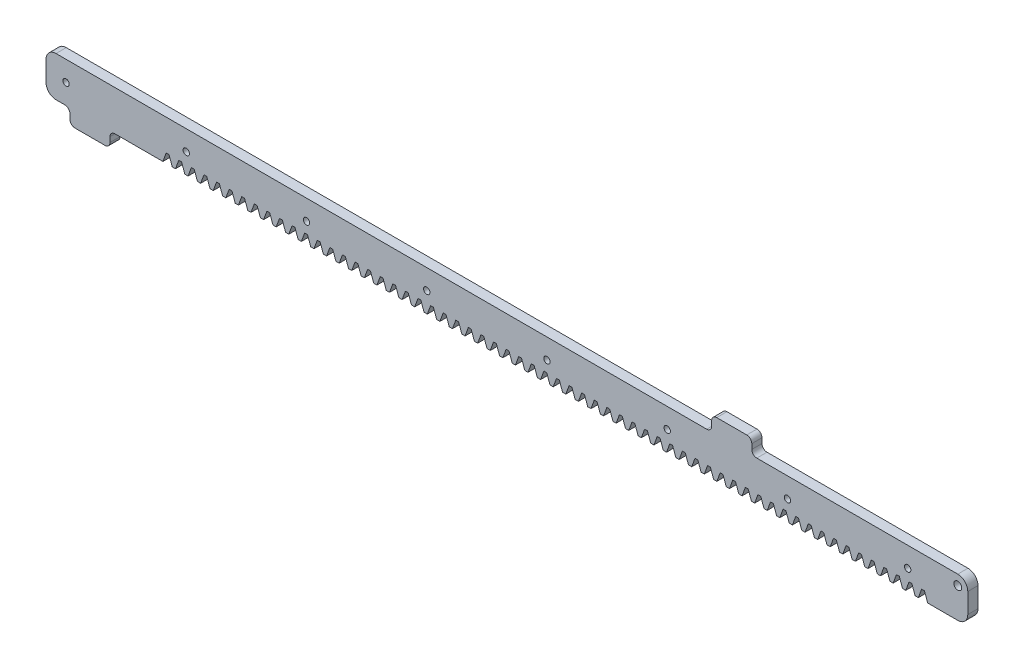
SolidWorks part; units mm, degrees
material "PC High Viscosity"
ref_plane "Front Plane" through (0, 0, 0) normal (0, 0, 1) x (1, 0, 0)
ref_plane "Top Plane" through (0, 0, 0) normal (0, 1, 0) x (1, 0, 0)
ref_plane "Right Plane" through (0, 0, 0) normal (1, 0, 0) x (0, 0, -1)
sketch "Sketch1" plane through (0, 0, 0) normal (0, 0, 1) x (1, 0, 0)
  line L1 (0, 0) -> (15.1307, 0)
  line L2 (0, 0) -> (0, 25.4)
  line L3 (0, 25.4) -> (40.5308, 25.4)
  line L4 (584.2, 0) -> (584.2, 25.4)
  line L7 (533.4, 25.4) -> (584.2, 25.4)
  line L8 (40.5308, 25.4) -> (421.9033, 25.4)
  line L9 (40.5307, 0) -> (584.2, 0)
  line L11 (584.2, 22.7162) -> (577.85, 26.3823) construction
  line L12 (577.85, 26.3823) -> (571.5, 22.7162) construction
  line L13 (571.5, 22.7162) -> (571.5, 15.3838) construction
  line L14 (571.5, 15.3838) -> (577.85, 11.7177) construction
  line L15 (577.85, 11.7177) -> (584.2, 15.3838) construction
  line L16 (584.2, 15.3838) -> (584.2, 22.7162) construction
  line L19 (590.55, 0) -> (590.55, 10.0162) construction
  line L20 (590.55, 10.0162) -> (76.2, 10.0162) construction
  line L21 (76.2, 10.0162) -> (76.2, 0) construction
  line L22 (447.3033, 25.4) -> (533.4, 25.4)
  line L26 (15.1307, 0) -> (15.1307, -9.525)
  line L27 (15.1307, -9.525) -> (40.5307, -9.525)
  line L28 (40.5307, -9.525) -> (40.5307, 0)
  line L29 (421.9033, 25.4) -> (421.9033, 34.925)
  line L30 (421.9033, 34.925) -> (447.3033, 34.925)
  line L31 (447.3033, 34.925) -> (447.3033, 25.4)
  circle A0 centre (577.85, 19.05) radius 2.4892
  circle A1 centre (577.85, 19.05) radius 6.35 construction
  dimension "D5" = 4.9784
  dimension "D6" = 40.5307
  dimension "D7" = 12.7
  dimension "D1" = 584.2
  dimension "D2" = 25.4
  dimension "D3" = 421.9033
  dimension "D4" = 9.525
  dimension "D8" = 25.4
  dimension "D9" = 25.4
extrude "Boss-Extrude1" add sketch "Sketch1" along normal blind 6.477 contours L3 | L1 L4 L3 L2 A0 | L1 region at (289.8115, 12.6919, 0)
fillet "Fillet2" radius 6.35 4 edges at (0, 0, 3.2385) (0, 25.4, 3.2385) (584.2, 25.4, 3.2385) (584.2, 0, 3.2385)
sketch "Sketch2" plane through (0, 0, 6.477) normal (0, 0, 1) x (1, 0, 0)
  line L0 (558.8, 0) -> (43.7057, 0)
  line L1 (43.7057, 0) -> (43.7057, 5.715)
  line L2 (43.7057, 5.715) -> (558.8, 5.715)
  line L3 (558.8, 5.715) -> (558.8, 0)
  line L5 (557.8755, 2.54) -> (549.711, 2.54) construction
  line L6 (558.8, 0) -> (556.7199, 5.715)
  line L7 (40.5307, 0) -> (552.8688, 0) construction
  line L8 (552.8688, 0) -> (558.8, 0)
  line L10 (556.7199, 5.715) -> (554.9488, 5.715)
  line L11 (558.8, 0) -> (552.8688, 0)
  line L12 (552.8688, 0) -> (554.9488, 5.715)
  line L13 (554.9488, 5.715) -> (556.7199, 5.715)
  line L14 (558.8, 0) -> (552.8688, 0)
  line L15 (554.9488, 5.715) -> (556.7199, 5.715)
  line L16 (558.8, 0) -> (552.8688, 0)
  line L17 (552.8688, 0) -> (558.8, 0)
  line L19 (556.7199, 5.715) -> (554.9488, 5.715) construction
  line L20 (552.8688, 0) -> (558.8, 0) construction
  line L21 (0, 0) -> (15.1307, 0) construction
  line L22 (584.2, 0) -> (584.2, 25.4) construction
  line L23 (40.5307, 0) -> (584.2, 0) construction
  point P8 (553.7932, 2.54)
  point P16 (557.8755, 2.54)
  dimension "D1" = 70
  dimension "D2" = 2.54
  dimension "D3" = 3.175
  dimension "D4" = 70
  dimension "D5" = 1.7711
  dimension "D6" = 25.4
extrude "Cut-Extrude1" cut sketch "Sketch2" against normal through all contours L12 L0 L8 L6 L2 region at (555.8344, 2.343, 6.477)
pattern_linear "LPattern1" count 61 spacing 7.9796 along (-1, 0, 0) of "Cut-Extrude1"
sketch "Sketch3" plane through (0, 0, 6.477) normal (0, 0, 1) x (1, 0, 0)
  line L2 (533.4, 25.4) -> (584.2, 25.4) construction
  line L3 (584.2, 0) -> (584.2, 25.4) construction
  circle A0 centre (546.1, 12.7) radius 2.0193
  dimension "D2" = 4.0386
  dimension "D1" = 12.7
  dimension "D3" = 38.1
extrude "Cut-Extrude2" cut sketch "Sketch3" against normal through all
pattern_linear "LPattern2" count 8 spacing 76.2 along (-1, 0, 0) of "Cut-Extrude2"
fillet "Fillet3" radius 3.175 8 edges at (421.9033, 25.4, 3.2385) (421.9033, 34.925, 3.2385) (447.3033, 34.925, 3.2385) (447.3033, 25.4, 3.2385) (40.5307, -9.525, 3.2385) (40.5307, 0, 3.2385) (15.1307, -9.525, 3.2385) (15.1307, 0, 3.2385)
